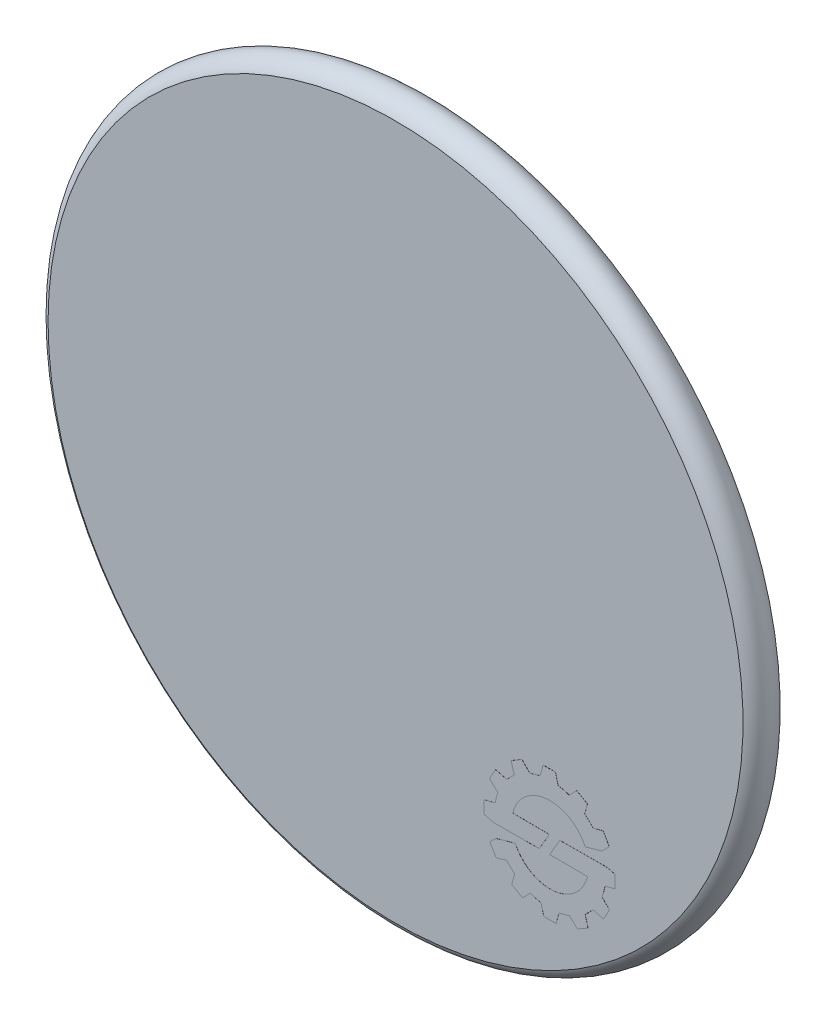
SolidWorks part; units mm, degrees
ref_plane "Front Plane" through (0, 0, 0) normal (0, 0, 1) x (1, 0, 0)
ref_plane "Top Plane" through (0, 0, 0) normal (0, 1, 0) x (1, 0, 0)
ref_plane "Right Plane" through (0, 0, 0) normal (1, 0, 0) x (0, 0, -1)
sketch "Sketch1" plane through (0, 0, 0) normal (0, 1, 0) x (1, 0, 0)
  line L0 (0, 0) -> (-40, 0)
  line L3 (-40, 0) -> (-42, 1.5)
  line L4 (0, 0) -> (0, -3)
  line L5 (0, -3) -> (-42, -3)
  line L6 (-42, -3) -> (-44.5, -3)
  line L8 (-44.5, 1.5) -> (-42, 1.5)
  arc A0 (-44.5, 1.5) -> (-44.5, -3) centre (-43.5625, -0.75) ccw
  dimension "D1" = 40
  dimension "D2" = 42
revolve "Revolve1" add sketch "Sketch1" angle 360 about L4
sketch "Sketch3" plane through (0, 0, 0) normal (0, 0, -1) x (-1, 0, 0)
  line L2 (23.1051, 6.1442) -> (23.4909, 5.3961)
  line L3 (23.4909, 5.3961) -> (22.7778, 4.7181)
  line L4 (-2.9032, -5.6502) -> (-4.1657, -5.0774)
  line L5 (-4.1657, -5.0774) -> (-4.5047, -4.3643)
  line L6 (-4.5047, -4.3643) -> (-4.8436, -3.6513)
  line L7 (-4.8436, -3.6513) -> (-4.2709, -2.5058)
  line L8 (-6.8776, -7.8243) -> (-6.8425, -8.5608)
  line L9 (-6.8425, -8.5608) -> (-7.8244, -9.4024)
  line L10 (-12.0559, -15.5158) -> (-12.4884, -16.334)
  line L11 (-12.4884, -16.334) -> (-12.4767, -17.877)
  line L12 (1.9244, -10.618) -> (3.7596, -10.6531)
  line L13 (3.7596, -10.6531) -> (4.7648, -11.6818)
  line L14 (-6.3749, -9.3322) -> (-5.8606, -8.9114)
  line L15 (-5.8606, -8.9114) -> (-5.5333, -9.1452)
  line L16 (11.416, -24.7386) -> (10.7731, -24.7502)
  line L17 (10.7731, -24.7502) -> (10.7965, -24.2359)
  line L18 (-8.1049, 2.9063) -> (-8.4439, 3.3271)
  line L19 (-8.4439, 3.3271) -> (-8.1049, 3.5726)
  arc A0 (-6.784, 21.8427) -> (7.1261, 21.3752) centre (-0.73, -5.1957) cw
  arc A1 (-9.5661, 22.322) -> (8.6573, 22.8831) centre (0.1955, 1.4952) cw
  spline S84 degree 3 poles (7.1261, 21.3752) (7.617, 21.118) (8.3067, 20.6855) (8.6456, 20.4167) knots 0 0 0 0 1 1 1 1
  spline S85 degree 3 poles (8.6456, 20.4167) (9.6977, 19.5867) (11.1354, 18.1256) (11.4744, 17.5411) knots 0 0 0 0 1 1 1 1
  spline S86 degree 3 poles (11.4744, 17.5411) (12.655, 15.5189) (15.0162, 13.0642) (17.132, 11.6732) knots 0 0 0 0 1 1 1 1
  spline S87 degree 3 poles (17.132, 11.6732) (17.9268, 11.1589) (18.6399, 10.7264) (18.7217, 10.7264) knots 0 0 0 0 1 1 1 1
  spline S88 degree 3 poles (18.7217, 10.7264) (18.8035, 10.7264) (18.9321, 10.6445) (19.0256, 10.5393) knots 0 0 0 0 1 1 1 1
  spline S89 degree 3 poles (19.0256, 10.5393) (19.1074, 10.4458) (19.3763, 10.2588) (19.6218, 10.1302) knots 0 0 0 0 1 1 1 1
  spline S90 degree 3 poles (19.6218, 10.1302) (19.8672, 10.0016) (20.1712, 9.8029) (20.2764, 9.6977) knots 0 0 0 0 1 1 1 1
  spline S91 degree 3 poles (20.2764, 9.6977) (20.3816, 9.5925) (20.7322, 9.2886) (21.0478, 9.0431) knots 0 0 0 0 1 1 1 1
  spline S92 degree 3 poles (21.0478, 9.0431) (21.6323, 8.5522) (22.4389, 7.4183) (23.1051, 6.1442) knots 0 0 0 0 1 1 1 1
  spline S93 degree 3 poles (22.7778, 4.7181) (21.9479, 3.935) (21.6206, 3.3388) (21.5154, 2.4271) knots 0 0 0 0 1 1 1 1
  spline S94 degree 3 poles (21.5154, 2.4271) (21.3985, 1.3867) (21.5855, 0.9192) (22.4739, 0.1009) knots 0 0 0 0 1 1 1 1
  spline S95 degree 3 poles (22.4739, 0.1009) (23.222, -0.5771) (23.2454, -0.6238) (23.1168, -0.9394) knots 0 0 0 0 1 1 1 1
  spline S96 degree 3 poles (23.1168, -0.9394) (22.7895, -1.7226) (20.8258, -3.476) (19.5399, -4.1189) knots 0 0 0 0 1 1 1 1
  spline S97 degree 3 poles (19.5399, -4.1189) (19.1542, -4.3176) (18.7568, -4.528) (18.6633, -4.5864) knots 0 0 0 0 1 1 1 1
  spline S98 degree 3 poles (18.6633, -4.5864) (18.1606, -4.8904) (16.2436, -5.5216) (15.7877, -5.5216) knots 0 0 0 0 1 1 1 1
  spline S99 degree 3 poles (15.7877, -5.5216) (15.6241, -5.5216) (15.3903, -5.58) (15.2734, -5.6385) knots 0 0 0 0 1 1 1 1
  spline S100 degree 3 poles (15.2734, -5.6385) (14.3149, -6.1528) (9.6275, -6.3515) (9.1717, -5.8956) knots 0 0 0 0 1 1 1 1
  spline S101 degree 3 poles (9.1717, -5.8956) (9.0898, -5.8138) (9.0314, -5.3229) (9.0314, -4.6215) knots 0 0 0 0 1 1 1 1
  spline S102 degree 3 poles (9.0314, -4.6215) (9.0197, -3.324) (8.7859, -2.646) (8.3183, -2.5291) knots 0 0 0 0 1 1 1 1
  spline S103 degree 3 poles (8.3183, -2.5291) (7.8742, -2.4239) (7.5936, -2.5759) (7.1377, -3.1954) knots 0 0 0 0 1 1 1 1
  spline S104 degree 3 poles (7.1377, -3.1954) (6.752, -3.7331) (6.7169, -3.8266) (6.7637, -4.3994) knots 0 0 0 0 1 1 1 1
  spline S105 degree 3 poles (6.7637, -4.3994) (6.8104, -4.9371) (6.8806, -5.0891) (7.2429, -5.4398) knots 0 0 0 0 1 1 1 1
  spline S106 degree 3 poles (7.2429, -5.4398) (7.4767, -5.6618) (7.6754, -5.8956) (7.6754, -5.9658) knots 0 0 0 0 1 1 1 1
  spline S107 degree 3 poles (7.6754, -5.9658) (7.6754, -6.0242) (7.465, -6.0827) (7.2196, -6.0827) knots 0 0 0 0 1 1 1 1
  spline S108 degree 3 poles (7.2196, -6.0827) (6.9624, -6.0827) (6.5182, -6.1762) (6.2143, -6.2697) knots 0 0 0 0 1 1 1 1
  spline S109 degree 3 poles (6.2143, -6.2697) (5.9221, -6.3749) (5.6065, -6.4567) (5.5246, -6.4567) knots 0 0 0 0 1 1 1 1
  spline S110 degree 3 poles (5.5246, -6.4567) (5.4311, -6.4567) (5.209, -6.5385) (5.0337, -6.632) knots 0 0 0 0 1 1 1 1
  spline S111 degree 3 poles (5.0337, -6.632) (4.7648, -6.7723) (4.4492, -6.7957) (3.5258, -6.7489) knots 0 0 0 0 1 1 1 1
  spline S112 degree 3 poles (3.5258, -6.7489) (2.8829, -6.7022) (2.0997, -6.6204) (1.7724, -6.5619) knots 0 0 0 0 1 1 1 1
  spline S113 degree 3 poles (1.7724, -6.5619) (1.4568, -6.5035) (0.6736, -6.4333) (0.0307, -6.3983) knots 0 0 0 0 1 1 1 1
  spline S114 degree 3 poles (0.0307, -6.3983) (-0.6005, -6.3749) (-1.1499, -6.3164) (-1.1849, -6.2814) knots 0 0 0 0 1 1 1 1
  spline S115 degree 3 poles (-1.1849, -6.2814) (-1.22, -6.2463) (-1.3369, -6.2229) (-1.4421, -6.2229) knots 0 0 0 0 1 1 1 1
  spline S116 degree 3 poles (-1.4421, -6.2229) (-1.559, -6.2229) (-2.2136, -5.9658) (-2.9032, -5.6502) knots 0 0 0 0 1 1 1 1
  spline S117 degree 3 poles (-4.2709, -2.5058) (-3.6397, -1.2433) (-3.5228, -0.8576) (-3.2539, 0.849) knots 0 0 0 0 1 1 1 1
  spline S118 degree 3 poles (-3.2539, 0.849) (-3.102, 1.7958) (-3.0903, 2.2751) (-3.1838, 3.4206) knots 0 0 0 0 1 1 1 1
  spline S119 degree 3 poles (-3.1838, 3.4206) (-3.4293, 6.2611) (-3.5578, 6.8105) (-4.0371, 7.1495) knots 0 0 0 0 1 1 1 1
  spline S120 degree 3 poles (-4.0371, 7.1495) (-4.5514, 7.5118) (-5.6034, 7.2897) (-5.8957, 6.7404) knots 0 0 0 0 1 1 1 1
  spline S121 degree 3 poles (-5.8957, 6.7404) (-5.9892, 6.5533) (-5.9892, 5.9689) (-5.884, 4.4843) knots 0 0 0 0 1 1 1 1
  spline S122 degree 3 poles (-5.884, 4.4843) (-5.7788, 2.8245) (-5.7788, 2.3219) (-5.919, 1.5504) knots 0 0 0 0 1 1 1 1
  spline S123 degree 3 poles (-5.919, 1.5504) (-6.0126, 1.036) (-6.1411, 0.4983) (-6.2113, 0.3581) knots 0 0 0 0 1 1 1 1
  spline S124 degree 3 poles (-6.2113, 0.3581) (-6.2931, 0.2178) (-6.3515, -0.0744) (-6.3515, -0.2848) knots 0 0 0 0 1 1 1 1
  spline S125 degree 3 poles (-6.3515, -0.2848) (-6.3515, -0.7407) (-6.6321, -1.7226) (-6.8776, -2.085) knots 0 0 0 0 1 1 1 1
  spline S126 degree 3 poles (-6.8776, -2.085) (-6.9711, -2.2252) (-7.123, -2.7162) (-7.2165, -3.1604) knots 0 0 0 0 1 1 1 1
  spline S127 degree 3 poles (-7.2165, -3.1604) (-7.5088, -4.5397) (-8.14, -5.5566) (-9.0284, -6.0827) knots 0 0 0 0 1 1 1 1
  spline S128 degree 3 poles (-9.0284, -6.0827) (-9.3206, -6.2463) (-9.8583, -6.6087) (-10.209, -6.8775) knots 0 0 0 0 1 1 1 1
  spline S129 degree 3 poles (-10.209, -6.8775) (-10.9688, -7.4503) (-11.635, -7.801) (-12.1961, -7.9179) knots 0 0 0 0 1 1 1 1
  spline S130 degree 3 poles (-12.1961, -7.9179) (-12.4182, -7.9646) (-12.6871, -8.0698) (-12.7806, -8.1516) knots 0 0 0 0 1 1 1 1
  spline S131 degree 3 poles (-12.7806, -8.1516) (-12.8741, -8.2335) (-13.2832, -8.362) (-13.6806, -8.4439) knots 0 0 0 0 1 1 1 1
  spline S132 degree 3 poles (-13.6806, -8.4439) (-14.0781, -8.514) (-14.5924, -8.6426) (-14.8028, -8.7361) knots 0 0 0 0 1 1 1 1
  spline S133 degree 3 poles (-14.8028, -8.7361) (-15.0249, -8.8296) (-15.5509, -8.9348) (-15.9717, -8.9816) knots 0 0 0 0 1 1 1 1
  spline S134 degree 3 poles (-15.9717, -8.9816) (-16.6614, -9.0517) (-16.8017, -9.0283) (-17.3277, -8.7478) knots 0 0 0 0 1 1 1 1
  spline S135 degree 3 poles (-17.3277, -8.7478) (-17.655, -8.5841) (-17.9823, -8.4439) (-18.0524, -8.4439) knots 0 0 0 0 1 1 1 1
  spline S136 degree 3 poles (-18.0524, -8.4439) (-18.1225, -8.4439) (-18.4264, -8.2685) (-18.7304, -8.0581) knots 0 0 0 0 1 1 1 1
  spline S137 degree 3 poles (-18.7304, -8.0581) (-19.0226, -7.8477) (-19.4083, -7.6022) (-19.572, -7.5204) knots 0 0 0 0 1 1 1 1
  spline S138 degree 3 poles (-19.572, -7.5204) (-19.7473, -7.4386) (-20.0279, -7.2282) (-20.2149, -7.0645) knots 0 0 0 0 1 1 1 1
  spline S139 degree 3 poles (-20.2149, -7.0645) (-20.5656, -6.7256) (-21.5007, -6.106) (-21.641, -6.106) knots 0 0 0 0 1 1 1 1
  spline S140 degree 3 poles (-21.641, -6.106) (-21.6877, -6.106) (-21.7929, -6.0008) (-21.8748, -5.8722) knots 0 0 0 0 1 1 1 1
  spline S141 degree 3 poles (-21.8748, -5.8722) (-21.9566, -5.7437) (-22.0852, -5.6385) (-22.167, -5.6385) knots 0 0 0 0 1 1 1 1
  spline S142 degree 3 poles (-22.167, -5.6385) (-22.2371, -5.6385) (-22.6462, -5.3579) (-23.067, -5.0189) knots 0 0 0 0 1 1 1 1
  spline S143 degree 3 poles (-23.067, -5.0189) (-23.6866, -4.528) (-23.9087, -4.2358) (-24.271, -3.5227) knots 0 0 0 0 1 1 1 1
  spline S144 degree 3 poles (-24.271, -3.5227) (-24.7269, -2.6344) (-24.7269, -2.6227) (-24.7269, -1.1849) knots 0 0 0 0 1 1 1 1
  spline S145 degree 3 poles (-24.7269, -1.1849) (-24.7269, 0.3698) (-24.4697, 1.7491) (-23.9788, 2.7076) knots 0 0 0 0 1 1 1 1
  spline S146 degree 3 poles (-23.9788, 2.7076) (-23.6164, 3.4323) (-22.8099, 4.6363) (-22.2956, 5.2441) knots 0 0 0 0 1 1 1 1
  spline S147 degree 3 poles (-22.2956, 5.2441) (-22.0501, 5.5481) (-21.7111, 5.9572) (-21.5475, 6.1676) knots 0 0 0 0 1 1 1 1
  spline S148 degree 3 poles (-21.5475, 6.1676) (-21.3838, 6.3663) (-21.1617, 6.6468) (-21.0331, 6.7871) knots 0 0 0 0 1 1 1 1
  spline S149 degree 3 poles (-21.0331, 6.7871) (-20.7877, 7.0677) (-19.6304, 8.5756) (-19.2681, 9.0782) knots 0 0 0 0 1 1 1 1
  spline S150 degree 3 poles (-19.2681, 9.0782) (-19.1395, 9.2535) (-18.7537, 9.6276) (-18.4148, 9.9198) knots 0 0 0 0 1 1 1 1
  spline S151 degree 3 poles (-18.4148, 9.9198) (-17.2926, 10.8432) (-16.7666, 11.4628) (-16.0769, 12.6551) knots 0 0 0 0 1 1 1 1
  spline S152 degree 3 poles (-16.0769, 12.6551) (-15.1184, 14.2916) (-15.1418, 14.2565) (-15.0717, 14.5955) knots 0 0 0 0 1 1 1 1
  spline S153 degree 3 poles (-15.0717, 14.5955) (-15.0366, 14.7708) (-14.8145, 15.1332) (-14.5924, 15.402) knots 0 0 0 0 1 1 1 1
  spline S154 degree 3 poles (-14.5924, 15.402) (-14.3703, 15.6709) (-14.2184, 15.9397) (-14.2534, 15.9982) knots 0 0 0 0 1 1 1 1
  spline S155 degree 3 poles (-14.2534, 15.9982) (-14.4755, 16.3722) (-12.6286, 18.1373) (-10.4428, 19.6452) knots 0 0 0 0 1 1 1 1
  spline S156 degree 3 poles (-10.4428, 19.6452) (-9.3089, 20.4167) (-7.7776, 21.3635) (-7.6607, 21.3635) knots 0 0 0 0 1 1 1 1
  spline S157 degree 3 poles (-7.6607, 21.3635) (-7.6023, 21.3635) (-7.4854, 21.4453) (-7.4036, 21.5388) knots 0 0 0 0 1 1 1 1
  spline S158 degree 3 poles (-7.4036, 21.5388) (-7.3217, 21.6323) (-7.0412, 21.7726) (-6.784, 21.8427) knots 0 0 0 0 1 1 1 1
  spline S163 degree 3 poles (-9.5661, 22.322) (-11.074, 21.3167) (-14.0664, 18.9789) (-14.4054, 18.5464) knots 0 0 0 0 1 1 1 1
  spline S164 degree 3 poles (-14.4054, 18.5464) (-14.6275, 18.2659) (-14.8846, 17.9853) (-14.9665, 17.9386) knots 0 0 0 0 1 1 1 1
  spline S165 degree 3 poles (-14.9665, 17.9386) (-15.0483, 17.8918) (-15.2002, 17.6814) (-15.3054, 17.471) knots 0 0 0 0 1 1 1 1
  spline S166 degree 3 poles (-15.3054, 17.471) (-15.4106, 17.2606) (-15.8198, 16.6995) (-16.2172, 16.2203) knots 0 0 0 0 1 1 1 1
  spline S167 degree 3 poles (-16.2172, 16.2203) (-16.6029, 15.741) (-17.4796, 14.6188) (-18.1576, 13.7188) knots 0 0 0 0 1 1 1 1
  spline S168 degree 3 poles (-18.1576, 13.7188) (-18.8356, 12.8187) (-19.759, 11.755) (-20.25, 11.3225) knots 0 0 0 0 1 1 1 1
  spline S169 degree 3 poles (-20.25, 11.3225) (-22.845, 8.9964) (-24.9373, 6.8572) (-24.9373, 6.5416) knots 0 0 0 0 1 1 1 1
  spline S170 degree 3 poles (-24.9373, 6.5416) (-24.9373, 6.4715) (-24.9724, 6.4014) (-25.0191, 6.378) knots 0 0 0 0 1 1 1 1
  spline S171 degree 3 poles (-25.0191, 6.378) (-25.1828, 6.3079) (-26.1062, 4.8818) (-26.1764, 4.5779) knots 0 0 0 0 1 1 1 1
  spline S172 degree 3 poles (-26.1764, 4.5779) (-26.2231, 4.4259) (-26.4335, 3.935) (-26.6439, 3.5025) knots 0 0 0 0 1 1 1 1
  spline S173 degree 3 poles (-26.6439, 3.5025) (-26.866, 3.07) (-27.0414, 2.579) (-27.0414, 2.4154) knots 0 0 0 0 1 1 1 1
  spline S174 degree 3 poles (-27.0414, 2.4154) (-27.0414, 2.24) (-27.1232, 2.0413) (-27.2284, 1.9478) knots 0 0 0 0 1 1 1 1
  spline S175 degree 3 poles (-27.2284, 1.9478) (-27.3336, 1.866) (-27.3803, 1.7023) (-27.3453, 1.5737) knots 0 0 0 0 1 1 1 1
  spline S176 degree 3 poles (-27.3453, 1.5737) (-27.3102, 1.4452) (-27.3453, 1.2348) (-27.4037, 1.1062) knots 0 0 0 0 1 1 1 1
  spline S177 degree 3 poles (-27.4037, 1.1062) (-27.6024, 0.7555) (-27.6258, -2.12) (-27.4505, -2.5642) knots 0 0 0 0 1 1 1 1
  spline S178 degree 3 poles (-27.4505, -2.5642) (-27.3687, -2.7629) (-27.3219, -2.9616) (-27.357, -2.985) knots 0 0 0 0 1 1 1 1
  spline S179 degree 3 poles (-27.357, -2.985) (-27.4505, -3.0902) (-27.1349, -4.0487) (-26.7141, -4.9371) knots 0 0 0 0 1 1 1 1
  spline S180 degree 3 poles (-26.7141, -4.9371) (-25.627, -7.2048) (-24.2476, -8.5724) (-22.202, -9.4374) knots 0 0 0 0 1 1 1 1
  spline S181 degree 3 poles (-22.202, -9.4374) (-21.7462, -9.6245) (-21.1266, -9.9985) (-20.811, -10.2674) knots 0 0 0 0 1 1 1 1
  spline S182 degree 3 poles (-20.811, -10.2674) (-19.5837, -11.3194) (-18.0524, -11.8688) (-16.4627, -11.822) knots 0 0 0 0 1 1 1 1
  spline S183 degree 3 poles (-16.4627, -11.822) (-15.9951, -11.8103) (-15.4106, -11.7285) (-15.1652, -11.635) knots 0 0 0 0 1 1 1 1
  spline S184 degree 3 poles (-15.1652, -11.635) (-14.908, -11.5415) (-14.4755, -11.3895) (-14.1833, -11.296) knots 0 0 0 0 1 1 1 1
  spline S185 degree 3 poles (-14.1833, -11.296) (-13.8911, -11.2025) (-13.4469, -11.0038) (-13.1897, -10.8401) knots 0 0 0 0 1 1 1 1
  spline S186 degree 3 poles (-13.1897, -10.8401) (-12.9325, -10.6882) (-12.278, -10.3141) (-11.7286, -10.0102) knots 0 0 0 0 1 1 1 1
  spline S187 degree 3 poles (-11.7286, -10.0102) (-10.6298, -9.4024) (-10.2674, -9.1452) (-9.1803, -8.2451) knots 0 0 0 0 1 1 1 1
  spline S188 degree 3 poles (-9.1803, -8.2451) (-8.7829, -7.9062) (-8.3855, -7.6256) (-8.3036, -7.6256) knots 0 0 0 0 1 1 1 1
  spline S189 degree 3 poles (-8.3036, -7.6256) (-8.2335, -7.6139) (-7.9646, -7.3685) (-7.7309, -7.0645) knots 0 0 0 0 1 1 1 1
  spline S190 degree 3 poles (-7.7309, -7.0645) (-7.4854, -6.7606) (-7.1698, -6.3866) (-7.0178, -6.2229) knots 0 0 0 0 1 1 1 1
  spline S191 degree 3 poles (-7.0178, -6.2229) (-6.8776, -6.0593) (-6.6087, -5.732) (-6.4217, -5.4865) knots 0 0 0 0 1 1 1 1
  spline S192 degree 3 poles (-6.4217, -5.4865) (-6.2347, -5.2527) (-6.0126, -5.054) (-5.9307, -5.054) knots 0 0 0 0 1 1 1 1
  spline S193 degree 3 poles (-5.9307, -5.054) (-5.6502, -5.054) (-5.7554, -5.4514) (-6.1061, -5.7904) knots 0 0 0 0 1 1 1 1
  spline S194 degree 3 poles (-6.1061, -5.7904) (-6.6555, -6.3047) (-6.9126, -6.9827) (-6.8776, -7.8243) knots 0 0 0 0 1 1 1 1
  spline S195 degree 3 poles (-7.8244, -9.4024) (-8.3971, -9.8933) (-9.005, -10.5596) (-9.2738, -10.957) knots 0 0 0 0 1 1 1 1
  spline S196 degree 3 poles (-9.2738, -10.957) (-9.8349, -11.8337) (-10.5246, -12.8156) (-10.9337, -13.365) knots 0 0 0 0 1 1 1 1
  spline S197 degree 3 poles (-10.9337, -13.365) (-11.109, -13.5871) (-11.3428, -13.9845) (-11.448, -14.2417) knots 0 0 0 0 1 1 1 1
  spline S198 degree 3 poles (-11.448, -14.2417) (-11.5532, -14.4872) (-11.8221, -15.0599) (-12.0559, -15.5158) knots 0 0 0 0 1 1 1 1
  spline S199 degree 3 poles (-12.4767, -17.877) (-12.4767, -19.0226) (-12.5117, -19.4317) (-12.6169, -19.4317) knots 0 0 0 0 1 1 1 1
  spline S200 degree 3 poles (-12.6169, -19.4317) (-12.839, -19.4317) (-13.4702, -18.6485) (-13.7391, -18.0407) knots 0 0 0 0 1 1 1 1
  spline S201 degree 3 poles (-13.7391, -18.0407) (-14.9898, -15.1768) (-15.5275, -14.6157) (-16.6263, -15.0599) knots 0 0 0 0 1 1 1 1
  spline S202 degree 3 poles (-16.6263, -15.0599) (-17.4446, -15.3872) (-17.9238, -16.4393) (-17.9238, -17.877) knots 0 0 0 0 1 1 1 1
  spline S203 degree 3 poles (-17.9238, -17.877) (-17.9238, -18.1576) (-17.9823, -18.6251) (-18.0524, -18.9057) knots 0 0 0 0 1 1 1 1
  spline S204 degree 3 poles (-18.0524, -18.9057) (-18.1576, -19.3265) (-18.1459, -19.5252) (-17.9939, -19.9694) knots 0 0 0 0 1 1 1 1
  spline S205 degree 3 poles (-17.9939, -19.9694) (-17.8186, -20.4954) (-17.0237, -21.7695) (-16.8835, -21.7695) knots 0 0 0 0 1 1 1 1
  spline S206 degree 3 poles (-16.8835, -21.7695) (-16.8367, -21.7695) (-16.5445, -21.9916) (-16.2289, -22.2605) knots 0 0 0 0 1 1 1 1
  spline S207 degree 3 poles (-16.2289, -22.2605) (-15.5743, -22.7982) (-13.3417, -23.9203) (-12.5468, -24.0957) knots 0 0 0 0 1 1 1 1
  spline S208 degree 3 poles (-12.5468, -24.0957) (-12.2546, -24.1658) (-11.8221, -24.2242) (-11.5766, -24.2242) knots 0 0 0 0 1 1 1 1
  spline S209 degree 3 poles (-11.5766, -24.2242) (-11.2961, -24.2242) (-11.109, -24.2827) (-11.074, -24.3996) knots 0 0 0 0 1 1 1 1
  spline S210 degree 3 poles (-11.074, -24.3996) (-11.0155, -24.5515) (-10.6882, -24.8087) (-9.4609, -25.7204) knots 0 0 0 0 1 1 1 1
  spline S211 degree 3 poles (-9.4609, -25.7204) (-9.2621, -25.8607) (-8.8881, -26.0361) (-8.6309, -26.1062) knots 0 0 0 0 1 1 1 1
  spline S212 degree 3 poles (-8.6309, -26.1062) (-8.1984, -26.2231) (-6.936, -26.7491) (-5.8255, -27.2751) knots 0 0 0 0 1 1 1 1
  spline S213 degree 3 poles (-5.8255, -27.2751) (-5.1826, -27.579) (-4.4462, -27.7193) (-3.5812, -27.731) knots 0 0 0 0 1 1 1 1
  spline S214 degree 3 poles (-3.5812, -27.731) (-3.1838, -27.731) (-2.7279, -27.7894) (-2.5643, -27.8596) knots 0 0 0 0 1 1 1 1
  spline S215 degree 3 poles (-2.5643, -27.8596) (-2.3422, -27.9648) (-2.1434, -27.9648) (-1.7577, -27.8596) knots 0 0 0 0 1 1 1 1
  spline S216 degree 3 poles (-1.7577, -27.8596) (-1.0797, -27.6608) (-0.4135, -27.8479) (0.3697, -28.4206) knots 0 0 0 0 1 1 1 1
  spline S217 degree 3 poles (0.3697, -28.4206) (1.7841, -29.461) (2.053, -29.6012) (3.1401, -29.8818) knots 0 0 0 0 1 1 1 1
  spline S218 degree 3 poles (3.1401, -29.8818) (4.2038, -30.1623) (5.7234, -30.0922) (6.6702, -29.7298) knots 0 0 0 0 1 1 1 1
  spline S219 degree 3 poles (6.6702, -29.7298) (7.6287, -29.3558) (9.2535, -27.8829) (9.686, -27.0179) knots 0 0 0 0 1 1 1 1
  spline S220 degree 3 poles (9.686, -27.0179) (10.2237, -25.9192) (10.212, -25.9308) (10.9484, -26.3049) knots 0 0 0 0 1 1 1 1
  spline S221 degree 3 poles (10.9484, -26.3049) (11.5329, -26.5971) (11.7082, -26.6205) (12.8771, -26.6205) knots 0 0 0 0 1 1 1 1
  spline S222 degree 3 poles (12.8771, -26.6205) (14.1512, -26.6088) (14.1746, -26.6088) (14.9695, -26.1646) knots 0 0 0 0 1 1 1 1
  spline S223 degree 3 poles (14.9695, -26.1646) (16.2436, -25.4516) (17.1437, -24.3177) (17.4827, -22.9969) knots 0 0 0 0 1 1 1 1
  spline S224 degree 3 poles (17.4827, -22.9969) (17.8216, -21.6643) (17.7515, -19.5018) (17.3073, -17.9355) knots 0 0 0 0 1 1 1 1
  spline S225 degree 3 poles (17.3073, -17.9355) (17.0618, -17.0822) (16.4189, -16.112) (15.7643, -15.6444) knots 0 0 0 0 1 1 1 1
  spline S226 degree 3 poles (15.7643, -15.6444) (15.2968, -15.2937) (15.0747, -15.2236) (14.0694, -15.095) knots 0 0 0 0 1 1 1 1
  spline S227 degree 3 poles (14.0694, -15.095) (12.4212, -14.8846) (11.7199, -15.0482) (10.8198, -15.8197) knots 0 0 0 0 1 1 1 1
  spline S228 degree 3 poles (10.8198, -15.8197) (10.4575, -16.1353) (10.1302, -16.3925) (10.0834, -16.3925) knots 0 0 0 0 1 1 1 1
  spline S229 degree 3 poles (10.0834, -16.3925) (10.0483, -16.3925) (10.0133, -16.2873) (10.0133, -16.1704) knots 0 0 0 0 1 1 1 1
  spline S230 degree 3 poles (10.0133, -16.1704) (10.0133, -16.0418) (9.8029, -15.5275) (9.5457, -15.0249) knots 0 0 0 0 1 1 1 1
  spline S231 degree 3 poles (9.5457, -15.0249) (9.1717, -14.2884) (8.821, -13.8443) (7.6871, -12.7104) knots 0 0 0 0 1 1 1 1
  spline S232 degree 3 poles (7.6871, -12.7104) (6.2961, -11.3077) (5.3025, -10.431) (5.0921, -10.431) knots 0 0 0 0 1 1 1 1
  spline S233 degree 3 poles (5.0921, -10.431) (4.8817, -10.431) (4.9869, -10.1037) (5.2675, -9.9284) knots 0 0 0 0 1 1 1 1
  spline S234 degree 3 poles (5.2675, -9.9284) (5.4194, -9.8232) (5.6532, -9.4959) (5.7935, -9.2037) knots 0 0 0 0 1 1 1 1
  spline S235 degree 3 poles (5.7935, -9.2037) (6.0623, -8.6192) (6.0507, -8.1516) (5.735, -7.6607) knots 0 0 0 0 1 1 1 1
  spline S236 degree 3 poles (5.735, -7.6607) (5.5831, -7.4152) (5.5948, -7.4035) (6.3429, -7.3334) knots 0 0 0 0 1 1 1 1
  spline S237 degree 3 poles (6.3429, -7.3334) (7.2429, -7.2282) (7.8859, -7.3217) (8.4703, -7.6139) knots 0 0 0 0 1 1 1 1
  spline S238 degree 3 poles (8.4703, -7.6139) (9.0898, -7.9179) (10.3289, -8.0231) (12.8771, -7.988) knots 0 0 0 0 1 1 1 1
  spline S239 degree 3 poles (12.8771, -7.988) (14.6539, -7.9529) (15.2383, -7.9062) (15.7994, -7.7308) knots 0 0 0 0 1 1 1 1
  spline S240 degree 3 poles (15.7994, -7.7308) (16.1852, -7.6139) (16.6293, -7.5087) (16.793, -7.5087) knots 0 0 0 0 1 1 1 1
  spline S241 degree 3 poles (16.793, -7.5087) (16.9566, -7.5087) (17.1904, -7.4386) (17.319, -7.3568) knots 0 0 0 0 1 1 1 1
  spline S242 degree 3 poles (17.319, -7.3568) (17.4476, -7.2633) (17.8918, -7.0762) (18.3126, -6.9243) knots 0 0 0 0 1 1 1 1
  spline S243 degree 3 poles (18.3126, -6.9243) (19.5166, -6.4801) (20.0075, -6.1645) (21.1063, -5.1475) knots 0 0 0 0 1 1 1 1
  spline S244 degree 3 poles (21.1063, -5.1475) (21.457, -4.8202) (21.9245, -4.4812) (22.1466, -4.3877) knots 0 0 0 0 1 1 1 1
  spline S245 degree 3 poles (22.1466, -4.3877) (23.0934, -3.9903) (24.3091, -2.7746) (24.9286, -1.6174) knots 0 0 0 0 1 1 1 1
  spline S246 degree 3 poles (24.9286, -1.6174) (25.1391, -1.22) (25.2793, -1.1148) (25.6884, -0.9979) knots 0 0 0 0 1 1 1 1
  spline S247 degree 3 poles (25.6884, -0.9979) (25.969, -0.9277) (26.5651, -0.6823) (27.0093, -0.4602) knots 0 0 0 0 1 1 1 1
  spline S248 degree 3 poles (27.0093, -0.4602) (27.7808, -0.0744) (27.8392, -0.016) (28.0613, 0.5802) knots 0 0 0 0 1 1 1 1
  spline S249 degree 3 poles (28.0613, 0.5802) (28.225, 1.0244) (28.2834, 1.4452) (28.2717, 2.0647) knots 0 0 0 0 1 1 1 1
  spline S250 degree 3 poles (28.2717, 2.0647) (28.2484, 2.8011) (28.1899, 3.0115) (27.8977, 3.4674) knots 0 0 0 0 1 1 1 1
  spline S251 degree 3 poles (27.8977, 3.4674) (27.3951, 4.2623) (27.1028, 4.5194) (26.308, 4.8935) knots 0 0 0 0 1 1 1 1
  spline S252 degree 3 poles (26.308, 4.8935) (25.9105, 5.0688) (25.5482, 5.3143) (25.5014, 5.4312) knots 0 0 0 0 1 1 1 1
  spline S253 degree 3 poles (25.5014, 5.4312) (25.4547, 5.5481) (25.3962, 5.9338) (25.3728, 6.2962) knots 0 0 0 0 1 1 1 1
  spline S254 degree 3 poles (25.3728, 6.2962) (25.3378, 7.0326) (25.0455, 7.7106) (24.578, 8.1431) knots 0 0 0 0 1 1 1 1
  spline S255 degree 3 poles (24.578, 8.1431) (24.4143, 8.3067) (24.2741, 8.482) (24.2741, 8.5405) knots 0 0 0 0 1 1 1 1
  spline S256 degree 3 poles (24.2741, 8.5405) (24.2741, 8.7158) (23.5493, 9.499) (22.8012, 10.1185) knots 0 0 0 0 1 1 1 1
  spline S257 degree 3 poles (22.8012, 10.1185) (21.9245, 10.8549) (20.5569, 11.6966) (19.0607, 12.433) knots 0 0 0 0 1 1 1 1
  spline S258 degree 3 poles (19.0607, 12.433) (17.4593, 13.2045) (16.6878, 13.672) (16.1852, 14.1747) knots 0 0 0 0 1 1 1 1
  spline S259 degree 3 poles (16.1852, 14.1747) (15.741, 14.6072) (13.5551, 17.7632) (12.8771, 18.9438) knots 0 0 0 0 1 1 1 1
  spline S260 degree 3 poles (12.8771, 18.9438) (12.0121, 20.4517) (11.5212, 21.0011) (10.7497, 21.3167) knots 0 0 0 0 1 1 1 1
  spline S261 degree 3 poles (10.7497, 21.3167) (10.5393, 21.4102) (10.1419, 21.7025) (9.8613, 21.9713) knots 0 0 0 0 1 1 1 1
  spline S262 degree 3 poles (9.8613, 21.9713) (9.5691, 22.2519) (9.0314, 22.661) (8.6573, 22.8831) knots 0 0 0 0 1 1 1 1
  spline S265 degree 3 poles (24.7416, 3.8882) (25.2443, 3.2921) (23.748, 2.2751) (23.187, 2.8362) knots 0 0 0 0 1 1 1 1
  spline S266 degree 3 poles (23.187, 2.8362) (22.8947, 3.1284) (22.9415, 3.4206) (23.3506, 3.7596) knots 0 0 0 0 1 1 1 1
  spline S267 degree 3 poles (23.3506, 3.7596) (23.7597, 4.1103) (24.5078, 4.1804) (24.7416, 3.8882) knots 0 0 0 0 1 1 1 1
  spline S287 degree 3 poles (-4.5163, -9.5076) (-4.1423, -9.5777) (-3.4176, -9.7063) (-2.9032, -9.8115) knots 0 0 0 0 1 1 1 1
  spline S288 degree 3 poles (-2.9032, -9.8115) (-2.3889, -9.9167) (-1.7343, -10.0336) (-1.4421, -10.092) knots 0 0 0 0 1 1 1 1
  spline S289 degree 3 poles (-1.4421, -10.092) (-0.5654, -10.244) (-0.2264, -10.3375) (-0.0628, -10.4661) knots 0 0 0 0 1 1 1 1
  spline S290 degree 3 poles (-0.0628, -10.4661) (0.0307, -10.5362) (0.884, -10.6064) (1.9244, -10.618) knots 0 0 0 0 1 1 1 1
  spline S291 degree 3 poles (4.7648, -11.6818) (5.3142, -12.2428) (6.0857, -13.0026) (6.4715, -13.365) knots 0 0 0 0 1 1 1 1
  spline S292 degree 3 poles (6.4715, -13.365) (7.465, -14.2884) (8.2482, -15.5275) (8.3768, -16.3691) knots 0 0 0 0 1 1 1 1
  spline S293 degree 3 poles (8.3768, -16.3691) (8.4352, -16.7315) (8.4703, -17.1406) (8.4352, -17.2692) knots 0 0 0 0 1 1 1 1
  spline S294 degree 3 poles (8.4352, -17.2692) (8.4119, -17.3978) (8.3885, -17.538) (8.3885, -17.5965) knots 0 0 0 0 1 1 1 1
  spline S295 degree 3 poles (8.3885, -17.5965) (8.3768, -17.69) (7.2429, -17.1172) (7.1377, -16.9653) knots 0 0 0 0 1 1 1 1
  spline S296 degree 3 poles (7.1377, -16.9653) (7.0559, -16.8133) (5.8402, -16.8367) (5.2792, -16.9886) knots 0 0 0 0 1 1 1 1
  spline S297 degree 3 poles (5.2792, -16.9886) (4.7298, -17.1406) (4.344, -17.4095) (3.5375, -18.216) knots 0 0 0 0 1 1 1 1
  spline S298 degree 3 poles (3.5375, -18.216) (2.2283, -19.5135) (1.9478, -19.946) (1.4802, -21.4071) knots 0 0 0 0 1 1 1 1
  spline S299 degree 3 poles (1.4802, -21.4071) (1.2581, -22.1319) (1.2581, -22.5877) (1.5153, -22.9034) knots 0 0 0 0 1 1 1 1
  spline S300 degree 3 poles (1.5153, -22.9034) (1.6906, -23.1371) (1.8075, -23.0787) (2.0179, -22.6696) knots 0 0 0 0 1 1 1 1
  spline S301 degree 3 poles (2.0179, -22.6696) (2.1231, -22.4709) (2.4153, -22.0734) (2.6608, -21.8046) knots 0 0 0 0 1 1 1 1
  spline S302 degree 3 poles (2.6608, -21.8046) (2.918, -21.524) (3.1167, -21.2552) (3.1167, -21.1967) knots 0 0 0 0 1 1 1 1
  spline S303 degree 3 poles (3.1167, -21.1967) (3.1167, -21.0448) (4.5661, -20.2499) (4.835, -20.2499) knots 0 0 0 0 1 1 1 1
  spline S304 degree 3 poles (4.835, -20.2499) (4.9636, -20.2499) (5.2324, -20.472) (5.4545, -20.7759) knots 0 0 0 0 1 1 1 1
  spline S305 degree 3 poles (5.4545, -20.7759) (5.6766, -21.0682) (5.887, -21.3019) (5.9455, -21.3019) knots 0 0 0 0 1 1 1 1
  spline S306 degree 3 poles (5.9455, -21.3019) (6.1091, -21.3019) (6.0507, -20.4837) (5.8519, -20.1213) knots 0 0 0 0 1 1 1 1
  spline S307 degree 3 poles (5.8519, -20.1213) (5.7117, -19.8408) (5.7, -19.7239) (5.8169, -19.5953) knots 0 0 0 0 1 1 1 1
  spline S308 degree 3 poles (5.8169, -19.5953) (6.0273, -19.3382) (6.1909, -19.3966) (6.5416, -19.8408) knots 0 0 0 0 1 1 1 1
  spline S309 degree 3 poles (6.5416, -19.8408) (6.9741, -20.3902) (7.1377, -20.3668) (7.0442, -19.7824) knots 0 0 0 0 1 1 1 1
  spline S310 degree 3 poles (7.0442, -19.7824) (6.9741, -19.3499) (6.9858, -19.3148) (7.1728, -19.42) knots 0 0 0 0 1 1 1 1
  spline S311 degree 3 poles (7.1728, -19.42) (7.7456, -19.7239) (8.5404, -20.7409) (8.8794, -21.6292) knots 0 0 0 0 1 1 1 1
  spline S312 degree 3 poles (8.8794, -21.6292) (9.008, -21.9565) (9.0781, -22.4709) (9.0781, -23.1605) knots 0 0 0 0 1 1 1 1
  spline S313 degree 3 poles (9.0781, -23.1605) (9.0781, -24.119) (9.0431, -24.2593) (8.6456, -25.0542) knots 0 0 0 0 1 1 1 1
  spline S314 degree 3 poles (8.6456, -25.0542) (8.0378, -26.2698) (6.939, -27.3569) (5.9455, -27.7193) knots 0 0 0 0 1 1 1 1
  spline S315 degree 3 poles (5.9455, -27.7193) (5.3025, -27.9414) (5.0805, -27.9765) (4.309, -27.8946) knots 0 0 0 0 1 1 1 1
  spline S316 degree 3 poles (4.309, -27.8946) (3.1868, -27.7894) (3.0933, -27.766) (0.3697, -26.679) knots 0 0 0 0 1 1 1 1
  spline S317 degree 3 poles (0.3697, -26.679) (-0.8343, -26.1997) (-1.6876, -25.9308) (-1.9214, -25.9659) knots 0 0 0 0 1 1 1 1
  spline S318 degree 3 poles (-1.9214, -25.9659) (-2.0266, -25.9776) (-2.3539, -25.9075) (-2.6578, -25.8023) knots 0 0 0 0 1 1 1 1
  spline S319 degree 3 poles (-2.6578, -25.8023) (-2.9617, -25.6971) (-3.3007, -25.6386) (-3.4176, -25.6854) knots 0 0 0 0 1 1 1 1
  spline S320 degree 3 poles (-3.4176, -25.6854) (-3.6163, -25.7438) (-5.1242, -25.3931) (-6.41, -24.9957) knots 0 0 0 0 1 1 1 1
  spline S321 degree 3 poles (-6.41, -24.9957) (-6.7256, -24.8905) (-7.4386, -24.5165) (-7.988, -24.1658) knots 0 0 0 0 1 1 1 1
  spline S322 degree 3 poles (-7.988, -24.1658) (-8.5257, -23.8151) (-9.0284, -23.5229) (-9.0985, -23.5229) knots 0 0 0 0 1 1 1 1
  spline S323 degree 3 poles (-9.0985, -23.5229) (-9.2972, -23.5229) (-10.1388, -22.5877) (-10.3492, -22.1202) knots 0 0 0 0 1 1 1 1
  spline S324 degree 3 poles (-10.3492, -22.1202) (-10.8051, -21.1266) (-10.9805, -18.2744) (-10.6415, -17.5965) knots 0 0 0 0 1 1 1 1
  spline S325 degree 3 poles (-10.6415, -17.5965) (-10.5246, -17.3861) (-10.4428, -17.0938) (-10.4428, -16.9419) knots 0 0 0 0 1 1 1 1
  spline S326 degree 3 poles (-10.4428, -16.9419) (-10.4428, -16.7315) (-10.3609, -16.6263) (-10.1388, -16.5795) knots 0 0 0 0 1 1 1 1
  spline S327 degree 3 poles (-10.1388, -16.5795) (-9.5193, -16.4159) (-7.9763, -14.6742) (-7.4854, -13.5871) knots 0 0 0 0 1 1 1 1
  spline S328 degree 3 poles (-7.4854, -13.5871) (-7.0763, -12.687) (-6.9009, -11.2376) (-7.1698, -11.0739) knots 0 0 0 0 1 1 1 1
  spline S329 degree 3 poles (-7.1698, -11.0739) (-7.3568, -10.957) (-7.2984, -10.244) (-7.0763, -9.9868) knots 0 0 0 0 1 1 1 1
  spline S330 degree 3 poles (-7.0763, -9.9868) (-6.9711, -9.8466) (-6.6438, -9.5543) (-6.3749, -9.3322) knots 0 0 0 0 1 1 1 1
  spline S331 degree 3 poles (-5.5333, -9.1452) (-5.3463, -9.2738) (-4.8904, -9.4374) (-4.5163, -9.5076) knots 0 0 0 0 1 1 1 1
  spline S341 degree 3 poles (13.7889, -16.6146) (13.9759, -16.7782) (14.198, -17.0588) (14.2915, -17.2341) knots 0 0 0 0 1 1 1 1
  spline S342 degree 3 poles (14.2915, -17.2341) (14.4785, -17.5848) (14.8058, -17.6783) (14.8058, -17.3861) knots 0 0 0 0 1 1 1 1
  spline S343 degree 3 poles (14.8058, -17.3861) (14.8058, -17.2809) (14.724, -17.0705) (14.6188, -16.9185) knots 0 0 0 0 1 1 1 1
  spline S344 degree 3 poles (14.6188, -16.9185) (14.3266, -16.4626) (14.6773, -16.5445) (15.1448, -17.0237) knots 0 0 0 0 1 1 1 1
  spline S345 degree 3 poles (15.1448, -17.0237) (15.6708, -17.5614) (16.0916, -19.1044) (15.9631, -20.0395) knots 0 0 0 0 1 1 1 1
  spline S346 degree 3 poles (15.9631, -20.0395) (15.8695, -20.7876) (15.3903, -22.6228) (15.2734, -22.7046) knots 0 0 0 0 1 1 1 1
  spline S347 degree 3 poles (15.2734, -22.7046) (15.2266, -22.7397) (15.1098, -22.915) (15.0045, -23.1138) knots 0 0 0 0 1 1 1 1
  spline S348 degree 3 poles (15.0045, -23.1138) (14.5136, -24.0723) (13.1109, -24.7152) (11.416, -24.7386) knots 0 0 0 0 1 1 1 1
  spline S349 degree 3 poles (10.7965, -24.2359) (10.8081, -23.9554) (10.9017, -23.6281) (11.0185, -23.5112) knots 0 0 0 0 1 1 1 1
  spline S350 degree 3 poles (11.0185, -23.5112) (11.1705, -23.3359) (11.1939, -23.1722) (11.1237, -22.6228) knots 0 0 0 0 1 1 1 1
  spline S351 degree 3 poles (11.1237, -22.6228) (11.0185, -21.7812) (10.8549, -21.3604) (10.1652, -20.2616) knots 0 0 0 0 1 1 1 1
  spline S352 degree 3 poles (10.1652, -20.2616) (9.6392, -19.4317) (9.6392, -19.3966) (9.8029, -19.0342) knots 0 0 0 0 1 1 1 1
  spline S353 degree 3 poles (9.8029, -19.0342) (9.9081, -18.8355) (10.0133, -18.5082) (10.06, -18.2978) knots 0 0 0 0 1 1 1 1
  spline S354 degree 3 poles (10.06, -18.2978) (10.1302, -18.0056) (10.2704, -17.8653) (10.7029, -17.6315) knots 0 0 0 0 1 1 1 1
  spline S355 degree 3 poles (10.7029, -17.6315) (11.0185, -17.4679) (11.4627, -17.2107) (11.7082, -17.0471) knots 0 0 0 0 1 1 1 1
  spline S356 degree 3 poles (11.7082, -17.0471) (12.2108, -16.7081) (12.4096, -16.673) (12.5031, -16.9068) knots 0 0 0 0 1 1 1 1
  spline S357 degree 3 poles (12.5031, -16.9068) (12.5966, -17.1406) (13.333, -18.1342) (13.4148, -18.1342) knots 0 0 0 0 1 1 1 1
  spline S358 degree 3 poles (13.4148, -18.1342) (13.7304, -18.1692) (13.5317, -17.0822) (13.1577, -16.673) knots 0 0 0 0 1 1 1 1
  spline S359 degree 3 poles (13.1577, -16.673) (12.7252, -16.2172) (13.2979, -16.1587) (13.7889, -16.6146) knots 0 0 0 0 1 1 1 1
  spline S360 degree 3 poles (-15.3639, -16.9419) (-15.2236, -17.1055) (-15.0833, -17.3861) (-15.0483, -17.5497) knots 0 0 0 0 1 1 1 1
  spline S361 degree 3 poles (-15.0483, -17.5497) (-15.0132, -17.7134) (-14.8145, -18.2277) (-14.5924, -18.6719) knots 0 0 0 0 1 1 1 1
  spline S362 degree 3 poles (-14.5924, -18.6719) (-14.2768, -19.3615) (-14.2184, -19.5953) (-14.2651, -20.0863) knots 0 0 0 0 1 1 1 1
  spline S363 degree 3 poles (-14.2651, -20.0863) (-14.3703, -21.1617) (-13.9027, -21.7578) (-12.5468, -22.2371) knots 0 0 0 0 1 1 1 1
  spline S364 degree 3 poles (-12.5468, -22.2371) (-12.1727, -22.3773) (-12.0091, -22.4942) (-11.9857, -22.6813) knots 0 0 0 0 1 1 1 1
  spline S365 degree 3 poles (-11.9857, -22.6813) (-11.939, -22.9852) (-12.0675, -22.9969) (-12.7572, -22.7631) knots 0 0 0 0 1 1 1 1
  spline S366 degree 3 poles (-12.7572, -22.7631) (-15.0366, -21.9682) (-16.0769, -20.6473) (-16.2172, -18.403) knots 0 0 0 0 1 1 1 1
  spline S367 degree 3 poles (-16.2172, -18.403) (-16.3107, -16.7665) (-15.96, -16.1704) (-15.3639, -16.9419) knots 0 0 0 0 1 1 1 1
  spline S368 degree 3 poles (-6.597, -13.5637) (-7.9763, -15.0482) (-8.5024, -15.8782) (-8.7011, -16.8951) knots 0 0 0 0 1 1 1 1
  spline S369 degree 3 poles (-8.7011, -16.8951) (-8.9465, -18.1692) (-8.9582, -19.3499) (-8.7361, -20.2616) knots 0 0 0 0 1 1 1 1
  spline S370 degree 3 poles (-8.7361, -20.2616) (-8.5608, -21.0097) (-8.4556, -21.1967) (-7.9763, -21.676) knots 0 0 0 0 1 1 1 1
  spline S371 degree 3 poles (-7.9763, -21.676) (-7.6607, -21.9799) (-7.088, -22.3773) (-6.6321, -22.5877) knots 0 0 0 0 1 1 1 1
  spline S372 degree 3 poles (-6.6321, -22.5877) (-5.9424, -22.915) (-5.7554, -22.9501) (-5.2177, -22.8917) knots 0 0 0 0 1 1 1 1
  spline S373 degree 3 poles (-5.2177, -22.8917) (-4.8787, -22.8566) (-4.4345, -22.7397) (-4.2241, -22.6579) knots 0 0 0 0 1 1 1 1
  spline S374 degree 3 poles (-4.2241, -22.6579) (-4.0137, -22.5644) (-3.7098, -22.4592) (-3.5461, -22.4241) knots 0 0 0 0 1 1 1 1
  spline S375 degree 3 poles (-3.5461, -22.4241) (-3.3825, -22.389) (-2.8799, -22.0267) (-2.424, -21.6059) knots 0 0 0 0 1 1 1 1
  spline S376 degree 3 poles (-2.424, -21.6059) (-0.9278, -20.2382) (-0.3082, -18.3913) (-0.6706, -16.334) knots 0 0 0 0 1 1 1 1
  spline S377 degree 3 poles (-0.6706, -16.334) (-0.881, -15.1067) (-1.1148, -14.5573) (-1.5239, -14.3703) knots 0 0 0 0 1 1 1 1
  spline S378 degree 3 poles (-1.5239, -14.3703) (-1.933, -14.1832) (-2.0266, -14.3936) (-2.0266, -15.5743) knots 0 0 0 0 1 1 1 1
  spline S379 degree 3 poles (-2.0266, -15.5743) (-2.0266, -16.9419) (-2.4357, -18.4615) (-2.9968, -19.2213) knots 0 0 0 0 1 1 1 1
  spline S380 degree 3 poles (-2.9968, -19.2213) (-3.3825, -19.7473) (-4.3527, -20.4253) (-4.5047, -20.2733) knots 0 0 0 0 1 1 1 1
  spline S381 degree 3 poles (-4.5047, -20.2733) (-4.5631, -20.2148) (-4.68, -19.6888) (-4.7384, -19.1161) knots 0 0 0 0 1 1 1 1
  spline S382 degree 3 poles (-4.7384, -19.1161) (-4.867, -18.0056) (-4.9255, -17.8653) (-5.1709, -18.029) knots 0 0 0 0 1 1 1 1
  spline S383 degree 3 poles (-5.1709, -18.029) (-5.2995, -18.0991) (-5.3346, -18.403) (-5.3229, -19.3031) knots 0 0 0 0 1 1 1 1
  spline S384 degree 3 poles (-5.3229, -19.3031) (-5.3112, -20.5071) (-5.358, -20.624) (-5.7554, -20.3785) knots 0 0 0 0 1 1 1 1
  spline S385 degree 3 poles (-5.7554, -20.3785) (-5.8957, -20.285) (-5.9074, -20.1213) (-5.7788, -19.2563) knots 0 0 0 0 1 1 1 1
  spline S386 degree 3 poles (-5.7788, -19.2563) (-5.6619, -18.5199) (-5.6619, -18.2043) (-5.7554, -18.1108) knots 0 0 0 0 1 1 1 1
  spline S387 degree 3 poles (-5.7554, -18.1108) (-5.9892, -17.877) (-6.3165, -18.3446) (-6.4684, -19.1511) knots 0 0 0 0 1 1 1 1
  spline S388 degree 3 poles (-6.4684, -19.1511) (-6.5503, -19.5603) (-6.6555, -19.8992) (-6.7022, -19.8992) knots 0 0 0 0 1 1 1 1
  spline S389 degree 3 poles (-6.7022, -19.8992) (-7.123, -19.8992) (-7.2867, -18.4147) (-7.0061, -17.1874) knots 0 0 0 0 1 1 1 1
  spline S390 degree 3 poles (-7.0061, -17.1874) (-6.8892, -16.7198) (-6.749, -16.1704) (-6.6788, -15.9834) knots 0 0 0 0 1 1 1 1
  spline S391 degree 3 poles (-6.6788, -15.9834) (-6.6204, -15.7847) (-6.5386, -15.5041) (-6.5035, -15.3405) knots 0 0 0 0 1 1 1 1
  spline S392 degree 3 poles (-6.5035, -15.3405) (-6.4801, -15.1768) (-6.3165, -14.8028) (-6.1645, -14.5105) knots 0 0 0 0 1 1 1 1
  spline S393 degree 3 poles (-6.1645, -14.5105) (-6.0126, -14.2066) (-5.884, -13.891) (-5.884, -13.7858) knots 0 0 0 0 1 1 1 1
  spline S394 degree 3 poles (-5.884, -13.7858) (-5.884, -13.6923) (-5.8022, -13.552) (-5.7086, -13.4702) knots 0 0 0 0 1 1 1 1
  spline S395 degree 3 poles (-5.7086, -13.4702) (-5.5099, -13.3066) (-5.5099, -12.8741) (-5.7203, -12.8039) knots 0 0 0 0 1 1 1 1
  spline S396 degree 3 poles (-5.7203, -12.8039) (-5.7905, -12.7805) (-6.1762, -13.1312) (-6.597, -13.5637) knots 0 0 0 0 1 1 1 1
  spline S397 degree 3 poles (-14.7677, 13.1109) (-15.2236, 12.807) (-16.0535, 11.9771) (-16.0535, 11.8251) knots 0 0 0 0 1 1 1 1
  spline S398 degree 3 poles (-16.0535, 11.8251) (-16.0535, 11.755) (-16.1237, 11.6264) (-16.2172, 11.5563) knots 0 0 0 0 1 1 1 1
  spline S399 degree 3 poles (-16.2172, 11.5563) (-16.3107, 11.4745) (-16.4159, 11.2641) (-16.4627, 11.0887) knots 0 0 0 0 1 1 1 1
  spline S400 degree 3 poles (-16.4627, 11.0887) (-16.5445, 10.7264) (-17.129, 10.1185) (-17.9589, 9.5691) knots 0 0 0 0 1 1 1 1
  spline S401 degree 3 poles (-17.9589, 9.5691) (-18.5667, 9.16) (-18.7421, 8.8444) (-18.7421, 8.1781) knots 0 0 0 0 1 1 1 1
  spline S402 degree 3 poles (-18.7421, 8.1781) (-18.7421, 7.7222) (-18.5901, 7.8976) (-21.5007, 4.9285) knots 0 0 0 0 1 1 1 1
  spline S403 degree 3 poles (-21.5007, 4.9285) (-21.9916, 4.4259) (-22.3657, 3.8882) (-22.7047, 3.2219) knots 0 0 0 0 1 1 1 1
  spline S404 degree 3 poles (-22.7047, 3.2219) (-23.1606, 2.2868) (-23.1839, 2.1816) (-23.1839, 1.1529) knots 0 0 0 0 1 1 1 1
  spline S405 degree 3 poles (-23.1839, 1.1529) (-23.1839, 0.3815) (-23.2424, -0.0277) (-23.3827, -0.2965) knots 0 0 0 0 1 1 1 1
  spline S406 degree 3 poles (-23.3827, -0.2965) (-23.8268, -1.1615) (-23.7684, -2.1434) (-23.2073, -3.2305) knots 0 0 0 0 1 1 1 1
  spline S407 degree 3 poles (-23.2073, -3.2305) (-22.6696, -4.2942) (-22.2956, -4.6332) (-21.5007, -4.8085) knots 0 0 0 0 1 1 1 1
  spline S408 degree 3 poles (-21.5007, -4.8085) (-21.1734, -4.8787) (-20.776, -5.3813) (-20.5422, -6.0125) knots 0 0 0 0 1 1 1 1
  spline S409 degree 3 poles (-20.5422, -6.0125) (-20.4136, -6.3749) (-18.6252, -7.4269) (-17.8654, -7.5906) knots 0 0 0 0 1 1 1 1
  spline S410 degree 3 poles (-17.8654, -7.5906) (-16.3925, -7.8945) (-15.5042, -7.6958) (-14.4404, -6.7957) knots 0 0 0 0 1 1 1 1
  spline S411 degree 3 poles (-14.4404, -6.7957) (-13.9846, -6.4216) (-13.9261, -6.3983) (-12.991, -6.3983) knots 0 0 0 0 1 1 1 1
  spline S412 degree 3 poles (-12.991, -6.3983) (-11.9039, -6.3983) (-11.1792, -6.1294) (-10.9688, -5.6618) knots 0 0 0 0 1 1 1 1
  spline S413 degree 3 poles (-10.9688, -5.6618) (-10.8869, -5.4748) (-10.7817, -5.4164) (-10.6064, -5.4514) knots 0 0 0 0 1 1 1 1
  spline S414 degree 3 poles (-10.6064, -5.4514) (-10.1973, -5.5566) (-9.4726, -5.2761) (-9.0284, -4.8319) knots 0 0 0 0 1 1 1 1
  spline S415 degree 3 poles (-9.0284, -4.8319) (-8.5491, -4.3527) (-8.2218, -3.4292) (-8.2218, -2.5291) knots 0 0 0 0 1 1 1 1
  spline S416 degree 3 poles (-8.2218, -2.5291) (-8.2218, -2.2252) (-8.1517, -1.8862) (-8.0699, -1.7927) knots 0 0 0 0 1 1 1 1
  spline S417 degree 3 poles (-8.0699, -1.7927) (-7.7192, -1.3953) (-7.5205, -0.6004) (-7.5205, 0.323) knots 0 0 0 0 1 1 1 1
  spline S418 degree 3 poles (-7.5205, 0.323) (-7.5205, 1.5737) (-7.7075, 2.4037) (-8.1049, 2.9063) knots 0 0 0 0 1 1 1 1
  spline S419 degree 3 poles (-8.1049, 3.5726) (-7.9062, 3.7246) (-7.6724, 4.0752) (-7.5322, 4.461) knots 0 0 0 0 1 1 1 1
  spline S420 degree 3 poles (-7.5322, 4.461) (-7.3217, 5.0454) (-7.3101, 5.2091) (-7.4153, 6.5884) knots 0 0 0 0 1 1 1 1
  spline S421 degree 3 poles (-7.4153, 6.5884) (-7.4737, 7.4183) (-7.4971, 8.295) (-7.4503, 8.5405) knots 0 0 0 0 1 1 1 1
  spline S422 degree 3 poles (-7.4503, 8.5405) (-7.3919, 8.9028) (-7.462, 9.1834) (-7.7542, 9.8847) knots 0 0 0 0 1 1 1 1
  spline S423 degree 3 poles (-7.7542, 9.8847) (-8.1634, 10.8432) (-8.7128, 11.4628) (-9.5427, 11.907) knots 0 0 0 0 1 1 1 1
  spline S424 degree 3 poles (-9.5427, 11.907) (-10.0687, 12.1875) (-11.2025, 12.2459) (-11.5766, 12.0122) knots 0 0 0 0 1 1 1 1
  spline S425 degree 3 poles (-11.5766, 12.0122) (-11.787, 11.8836) (-11.8688, 11.8953) (-12.1844, 12.1174) knots 0 0 0 0 1 1 1 1
  spline S426 degree 3 poles (-12.1844, 12.1174) (-12.3832, 12.2576) (-12.5819, 12.5031) (-12.6169, 12.6668) knots 0 0 0 0 1 1 1 1
  spline S427 degree 3 poles (-12.6169, 12.6668) (-12.6637, 12.8304) (-12.839, 13.0291) (-13.0261, 13.1226) knots 0 0 0 0 1 1 1 1
  spline S428 degree 3 poles (-13.0261, 13.1226) (-13.4702, 13.3564) (-14.4054, 13.3447) (-14.7677, 13.1109) knots 0 0 0 0 1 1 1 1
  spline S448 degree 3 poles (4.9051, 8.0729) (4.683, 7.9677) (4.4492, 7.6989) (4.3323, 7.4651) knots 0 0 0 0 1 1 1 1
  spline S449 degree 3 poles (4.3323, 7.4651) (4.2271, 7.2313) (4.0986, 7.0209) (4.0518, 6.9858) knots 0 0 0 0 1 1 1 1
  spline S450 degree 3 poles (4.0518, 6.9858) (4.0051, 6.9508) (3.9349, 6.565) (3.8998, 6.1091) knots 0 0 0 0 1 1 1 1
  spline S451 degree 3 poles (3.8998, 6.1091) (3.818, 4.9987) (4.0635, 4.1804) (4.648, 3.6544) knots 0 0 0 0 1 1 1 1
  spline S452 degree 3 poles (4.648, 3.6544) (5.2558, 3.105) (5.7701, 3.0232) (6.4715, 3.3739) knots 0 0 0 0 1 1 1 1
  spline S453 degree 3 poles (6.4715, 3.3739) (6.9624, 3.631) (7.0442, 3.7246) (7.3014, 4.4025) knots 0 0 0 0 1 1 1 1
  spline S454 degree 3 poles (7.3014, 4.4025) (7.5819, 5.1857) (7.5819, 5.2208) (7.2546, 6.3663) knots 0 0 0 0 1 1 1 1
  spline S455 degree 3 poles (7.2546, 6.3663) (6.9741, 7.3248) (6.0857, 8.2716) (5.4545, 8.2599) knots 0 0 0 0 1 1 1 1
  spline S456 degree 3 poles (5.4545, 8.2599) (5.361, 8.2599) (5.1155, 8.1781) (4.9051, 8.0729) knots 0 0 0 0 1 1 1 1
  point P2 (0, 0)
extrude "Boss-Extrude1" add sketch "Sketch3" along normal blind 0.01 contours S261 S262 A1 S163 S164 S165 S166 S167 S168 S169 S170 S171 S172 S173 S174 S175 S176 S177 S178 S179 S180 S181 S182 S183 S184 S185 S186 S187 S188 S189 S190 S191 S192 S193 S194 L8 L9 S195 S196 S197 S198 L10 L11 S199 S200 S201 S202 S203 S204 S205 S206 | S455 S456 S448 S449 S450 S451 S452 S453 S454 | S427 S428 S397 S398 S399 S400 S401 S402 S403 S404 S405 S406 S407 S408 S409 S410 S411 S412 S413 S414 S415 S416 S417 S418 L18 L19 S419 S420 S421 S422 S423 S424 S425 S426 | S395 S396 S368 S369 S370 S371 S372 S373 S374 S375 S376 S377 S378 S379 S380 S381 S382 S383 S384 S385 S386 S387 S388 S389 S390 S391 S392 S393 S394 region at (7.4572, -6.4517, 0) region at (14.8131, 2.1911, 0) region at (5.0323, -18.9831, 0) region at (-5.6406, 5.6403, 0)
sketch "Sketch5" plane through (0, 0, 3) normal (0, 0, 1) x (1, 0, 0)
  line L0 (16.6947, -18.7297) -> (16.1934, -18.2222)
  line L1 (16.1934, -18.2222) -> (16.1083, -18.2709)
  line L2 (14.8898, -18.991) -> (14.8169, -19.0457)
  line L3 (14.8169, -19.0457) -> (14.8685, -19.2432)
  line L4 (15.1116, -20.0667) -> (15.221, -20.4222)
  line L5 (15.221, -20.4222) -> (14.8777, -20.7655)
  line L6 (12.1187, -22.2757) -> (12.0518, -22.4124)
  line L7 (12.0518, -22.4124) -> (12.3374, -22.6859)
  line L8 (12.1004, -26.8973) -> (12.617, -27.0189)
  line L9 (12.617, -27.0189) -> (15.4915, -27.0189)
  line L10 (24.1878, -23.6491) -> (24.2911, -23.8497)
  line L11 (24.2911, -23.8497) -> (24.4856, -23.798)
  line L12 (25.543, -23.5093) -> (26.3999, -23.2723)
  line L13 (26.3999, -23.2723) -> (26.886, -22.8014)
  line L14 (26.6186, -21.0056) -> (26.5609, -20.9326)
  line L15 (26.5609, -20.9326) -> (26.2145, -21.0329)
  line L16 (24.4734, -20.4404) -> (24.2364, -20.2277)
  line L17 (24.2364, -20.2277) -> (24.3914, -19.6808)
  line L18 (23.4221, -18.3013) -> (23.1942, -18.1706)
  line L19 (23.1942, -18.1706) -> (22.7202, -18.6659)
  line L20 (22.7202, -18.6659) -> (22.2462, -19.1612)
  line L21 (22.2462, -19.1612) -> (22.0669, -19.0943)
  line L22 (20.5294, -17.5963) -> (20.496, -17.4778)
  line L23 (20.496, -17.4778) -> (19.6938, -17.4778)
  line L24 (20.3805, -25.8885) -> (19.7515, -26.9885)
  line L25 (19.7515, -26.9885) -> (22.1641, -26.9885)
  line L26 (12.4438, -29.0486) -> (12.0822, -29.4102)
  line L27 (12.0822, -29.4102) -> (12.2189, -29.6351)
  line L28 (14.747, -30.8961) -> (15.2544, -31.4035)
  line L29 (15.2544, -31.4035) -> (15.1299, -31.8623)
  line L30 (16.1721, -33.4697) -> (16.2906, -33.5274)
  line L31 (16.2906, -33.5274) -> (16.4608, -33.3482)
  line L32 (16.9408, -32.8438) -> (17.2538, -32.5156)
  line L33 (17.2538, -32.5156) -> (17.5273, -32.6098)
  line L34 (20.3562, -34.2202) -> (20.5871, -34.2202)
  line L35 (20.5871, -34.2202) -> (20.7451, -33.567)
  line L36 (25.2057, -30.4403) -> (25.3029, -30.3218)
  line L37 (25.3029, -30.3218) -> (25.6007, -30.4069)
  line L38 (26.2692, -30.5892) -> (26.6399, -30.6894)
  line L39 (26.6399, -30.6894) -> (26.7888, -30.4281)
  line L40 (26.6916, -28.5928) -> (26.4485, -28.3649)
  line L41 (26.4485, -28.3649) -> (26.5731, -27.9882)
  line L42 (27.5089, -26.7606) -> (28.1166, -26.6087)
  line L43 (28.1166, -26.6087) -> (28.1166, -25.8034)
  line L44 (28.1166, -25.8034) -> (28.1166, -24.9982)
  line L45 (28.1166, -24.9982) -> (27.6153, -24.8706)
  line L46 (27.6153, -24.8706) -> (27.1139, -24.746)
  line L47 (27.1139, -24.746) -> (24.1209, -24.746)
  spline S0 degree 3 poles (18.8916, -17.4839) (18.8916, -17.49) (18.8126, -17.7999) (18.7184, -18.1767) knots 0 0 0 0 1 1 1 1
  spline S1 degree 3 poles (18.7184, -18.1767) (18.5239, -18.9424) (18.5756, -18.8603) (18.2262, -18.9393) knots 0 0 0 0 1 1 1 1
  spline S2 degree 3 poles (18.2262, -18.9393) (18.135, -18.9576) (17.8737, -19.0335) (17.6488, -19.1065) knots 0 0 0 0 1 1 1 1
  spline S3 degree 3 poles (17.6488, -19.1065) (17.424, -19.1794) (17.2295, -19.2402) (17.2174, -19.2402) knots 0 0 0 0 1 1 1 1
  spline S4 degree 3 poles (17.2174, -19.2402) (17.2052, -19.2402) (16.9682, -19.0123) (16.6947, -18.7297) knots 0 0 0 0 1 1 1 1
  spline S5 degree 3 poles (16.1083, -18.2709) (15.3881, -18.6871) (14.9476, -18.9485) (14.8898, -18.991) knots 0 0 0 0 1 1 1 1
  spline S6 degree 3 poles (14.8685, -19.2432) (14.9232, -19.4529) (14.9415, -19.5197) (15.1116, -20.0667) knots 0 0 0 0 1 1 1 1
  spline S7 degree 3 poles (14.8777, -20.7655) (14.6893, -20.9539) (14.4796, -21.1727) (14.4128, -21.2517) knots 0 0 0 0 1 1 1 1
  spline S8 degree 3 poles (14.4128, -21.2517) (14.3459, -21.3307) (14.27, -21.3975) (14.2456, -21.3975) knots 0 0 0 0 1 1 1 1
  spline S9 degree 3 poles (14.2456, -21.3975) (14.2213, -21.3975) (14.0573, -21.355) (13.881, -21.3064) knots 0 0 0 0 1 1 1 1
  spline S10 degree 3 poles (13.881, -21.3064) (13.2399, -21.121) (12.8418, -21.0268) (12.8175, -21.0511) knots 0 0 0 0 1 1 1 1
  spline S11 degree 3 poles (12.8175, -21.0511) (12.8054, -21.0663) (12.7324, -21.1879) (12.6595, -21.3216) knots 0 0 0 0 1 1 1 1
  spline S12 degree 3 poles (12.6595, -21.3216) (12.5836, -21.4553) (12.4468, -21.6953) (12.3557, -21.8533) knots 0 0 0 0 1 1 1 1
  spline S13 degree 3 poles (12.3557, -21.8533) (12.2645, -22.0113) (12.1582, -22.2028) (12.1187, -22.2757) knots 0 0 0 0 1 1 1 1
  spline S14 degree 3 poles (12.3374, -22.6859) (12.4924, -22.8378) (12.7324, -23.0687) (12.8722, -23.2024) knots 0 0 0 0 1 1 1 1
  spline S15 degree 3 poles (12.8722, -23.2024) (13.009, -23.3331) (13.1214, -23.4486) (13.1214, -23.4546) knots 0 0 0 0 1 1 1 1
  spline S16 degree 3 poles (13.1214, -23.4546) (13.1214, -23.4638) (13.0819, -23.5792) (13.0333, -23.716) knots 0 0 0 0 1 1 1 1
  spline S17 degree 3 poles (13.0333, -23.716) (12.9877, -23.8527) (12.9178, -24.1019) (12.8783, -24.269) knots 0 0 0 0 1 1 1 1
  spline S18 degree 3 poles (12.8783, -24.269) (12.8418, -24.4361) (12.8023, -24.6123) (12.7902, -24.6609) knots 0 0 0 0 1 1 1 1
  spline S19 degree 3 poles (12.7902, -24.6609) (12.7689, -24.7491) (12.7568, -24.7551) (12.3162, -24.8645) knots 0 0 0 0 1 1 1 1
  spline S20 degree 3 poles (12.3162, -24.8645) (12.064, -24.9253) (11.7571, -25.0013) (11.6325, -25.0316) knots 0 0 0 0 1 1 1 1
  spline S21 degree 3 poles (11.6325, -25.0316) (11.5079, -25.059) (11.3864, -25.0955) (11.3651, -25.1137) knots 0 0 0 0 1 1 1 1
  spline S22 degree 3 poles (11.3651, -25.1137) (11.3377, -25.135) (11.3286, -25.3234) (11.3317, -25.8916) knots 0 0 0 0 1 1 1 1
  spline S23 degree 3 poles (11.3317, -25.8916) (11.3317, -26.3018) (11.3469, -26.6603) (11.359, -26.6877) knots 0 0 0 0 1 1 1 1
  spline S24 degree 3 poles (11.359, -26.6877) (11.3742, -26.715) (11.4319, -26.7454) (11.4866, -26.7545) knots 0 0 0 0 1 1 1 1
  spline S25 degree 3 poles (11.4866, -26.7545) (11.5413, -26.7636) (11.8178, -26.8274) (12.1004, -26.8973) knots 0 0 0 0 1 1 1 1
  spline S26 degree 3 poles (15.4915, -27.0189) (17.7461, -27.0189) (18.3781, -27.0097) (18.4145, -26.9794) knots 0 0 0 0 1 1 1 1
  spline S27 degree 3 poles (18.4145, -26.9794) (18.4389, -26.9611) (18.5969, -26.7029) (18.764, -26.4112) knots 0 0 0 0 1 1 1 1
  spline S28 degree 3 poles (18.764, -26.4112) (18.9311, -26.1195) (19.2076, -25.6394) (19.3778, -25.3446) knots 0 0 0 0 1 1 1 1
  spline S29 degree 3 poles (19.3778, -25.3446) (19.5449, -25.0499) (19.6847, -24.7977) (19.6847, -24.7886) knots 0 0 0 0 1 1 1 1
  spline S30 degree 3 poles (19.6847, -24.7886) (19.6847, -24.7794) (18.6394, -24.7703) (17.3602, -24.7703) knots 0 0 0 0 1 1 1 1
  spline S31 degree 3 poles (17.3602, -24.7703) (15.139, -24.7703) (15.0357, -24.7673) (15.0357, -24.7156) knots 0 0 0 0 1 1 1 1
  spline S32 degree 3 poles (15.0357, -24.7156) (15.0357, -24.6458) (15.218, -24.1079) (15.3152, -23.8892) knots 0 0 0 0 1 1 1 1
  spline S33 degree 3 poles (15.3152, -23.8892) (16.1295, -22.0691) (18.0074, -20.8992) (19.9733, -20.9843) knots 0 0 0 0 1 1 1 1
  spline S34 degree 3 poles (19.9733, -20.9843) (21.4926, -21.0481) (22.7809, -21.7105) (23.7077, -22.8955) knots 0 0 0 0 1 1 1 1
  spline S35 degree 3 poles (23.7077, -22.8955) (23.8171, -23.0384) (23.9082, -23.1599) (23.9082, -23.169) knots 0 0 0 0 1 1 1 1
  spline S36 degree 3 poles (23.9082, -23.169) (23.9082, -23.1781) (23.9478, -23.245) (23.9964, -23.3179) knots 0 0 0 0 1 1 1 1
  spline S37 degree 3 poles (23.9964, -23.3179) (24.0419, -23.3908) (24.1301, -23.5397) (24.1878, -23.6491) knots 0 0 0 0 1 1 1 1
  spline S38 degree 3 poles (24.4856, -23.798) (24.595, -23.7706) (25.069, -23.64) (25.543, -23.5093) knots 0 0 0 0 1 1 1 1
  spline S39 degree 3 poles (26.886, -22.8014) (27.1534, -22.54) (27.3722, -22.3182) (27.3722, -22.3061) knots 0 0 0 0 1 1 1 1
  spline S40 degree 3 poles (27.3722, -22.3061) (27.3722, -22.2909) (27.2324, -22.0447) (27.0653, -21.7561) knots 0 0 0 0 1 1 1 1
  spline S41 degree 3 poles (27.0653, -21.7561) (26.8951, -21.4674) (26.7371, -21.197) (26.7159, -21.1545) knots 0 0 0 0 1 1 1 1
  spline S42 degree 3 poles (26.7159, -21.1545) (26.6916, -21.1119) (26.649, -21.0451) (26.6186, -21.0056) knots 0 0 0 0 1 1 1 1
  spline S43 degree 3 poles (26.2145, -21.0329) (26.0231, -21.0846) (25.7648, -21.1636) (25.6372, -21.2031) knots 0 0 0 0 1 1 1 1
  spline S44 degree 3 poles (25.6372, -21.2031) (25.5096, -21.2426) (25.385, -21.276) (25.3576, -21.276) knots 0 0 0 0 1 1 1 1
  spline S45 degree 3 poles (25.3576, -21.276) (25.3333, -21.276) (25.2513, -21.2122) (25.1784, -21.1332) knots 0 0 0 0 1 1 1 1
  spline S46 degree 3 poles (25.1784, -21.1332) (24.9596, -20.8962) (24.7256, -20.6652) (24.4734, -20.4404) knots 0 0 0 0 1 1 1 1
  spline S47 degree 3 poles (24.3914, -19.6808) (24.6071, -18.912) (24.6041, -18.9637) (24.4643, -18.8907) knots 0 0 0 0 1 1 1 1
  spline S48 degree 3 poles (24.4643, -18.8907) (24.4005, -18.8573) (24.1908, -18.7388) (23.9994, -18.6294) knots 0 0 0 0 1 1 1 1
  spline S49 degree 3 poles (23.9994, -18.6294) (23.808, -18.52) (23.5467, -18.3711) (23.4221, -18.3013) knots 0 0 0 0 1 1 1 1
  spline S50 degree 3 poles (22.0669, -19.0943) (21.8299, -19.0092) (21.3467, -18.8847) (21.1584, -18.8603) knots 0 0 0 0 1 1 1 1
  spline S51 degree 3 poles (21.1584, -18.8603) (20.815, -18.8148) (20.8363, -18.8421) (20.6935, -18.3043) knots 0 0 0 0 1 1 1 1
  spline S52 degree 3 poles (20.6935, -18.3043) (20.6236, -18.0399) (20.5658, -17.7999) (20.5658, -17.7695) knots 0 0 0 0 1 1 1 1
  spline S53 degree 3 poles (20.5658, -17.7695) (20.5658, -17.7391) (20.5506, -17.6601) (20.5294, -17.5963) knots 0 0 0 0 1 1 1 1
  spline S54 degree 3 poles (19.6938, -17.4778) (19.2562, -17.4778) (18.8946, -17.4808) (18.8916, -17.4839) knots 0 0 0 0 1 1 1 1
  spline S55 degree 3 poles (21.0702, -24.7673) (21.0368, -24.7794) (20.7542, -25.2413) (20.3805, -25.8885) knots 0 0 0 0 1 1 1 1
  spline S56 degree 3 poles (22.1641, -26.9885) (24.1453, -26.9885) (24.5767, -26.9946) (24.5767, -27.028) knots 0 0 0 0 1 1 1 1
  spline S57 degree 3 poles (24.5767, -27.028) (24.5767, -27.0523) (24.5433, -27.1829) (24.5008, -27.3197) knots 0 0 0 0 1 1 1 1
  spline S58 degree 3 poles (24.5008, -27.3197) (24.285, -28.0398) (23.8171, -28.8116) (23.2762, -29.3494) knots 0 0 0 0 1 1 1 1
  spline S59 degree 3 poles (23.2762, -29.3494) (22.5774, -30.0361) (21.8238, -30.4433) (20.8089, -30.6834) knots 0 0 0 0 1 1 1 1
  spline S60 degree 3 poles (20.8089, -30.6834) (20.3228, -30.7958) (19.5631, -30.814) (19.0466, -30.7259) knots 0 0 0 0 1 1 1 1
  spline S61 degree 3 poles (19.0466, -30.7259) (17.6124, -30.4767) (16.5306, -29.787) (15.7011, -28.5837) knots 0 0 0 0 1 1 1 1
  spline S62 degree 3 poles (15.7011, -28.5837) (15.6434, -28.4986) (15.5401, -28.3254) (15.4763, -28.1978) knots 0 0 0 0 1 1 1 1
  spline S63 degree 3 poles (15.4763, -28.1978) (15.4094, -28.0672) (15.3395, -27.9608) (15.3243, -27.9608) knots 0 0 0 0 1 1 1 1
  spline S64 degree 3 poles (15.3243, -27.9608) (15.3061, -27.9608) (15.1754, -27.9942) (15.0357, -28.0337) knots 0 0 0 0 1 1 1 1
  spline S65 degree 3 poles (15.0357, -28.0337) (14.8929, -28.0763) (14.3672, -28.2191) (13.8658, -28.3558) knots 0 0 0 0 1 1 1 1
  spline S66 degree 3 poles (13.8658, -28.3558) (13.3645, -28.4956) (12.9208, -28.6232) (12.8783, -28.6445) knots 0 0 0 0 1 1 1 1
  spline S67 degree 3 poles (12.8783, -28.6445) (12.8358, -28.6688) (12.6413, -28.8481) (12.4438, -29.0486) knots 0 0 0 0 1 1 1 1
  spline S68 degree 3 poles (12.2189, -29.6351) (12.3496, -29.8538) (12.5289, -30.1577) (12.6352, -30.3461) knots 0 0 0 0 1 1 1 1
  spline S69 degree 3 poles (12.6352, -30.3461) (12.6626, -30.3947) (12.7324, -30.5102) (12.7871, -30.6013) knots 0 0 0 0 1 1 1 1
  spline S70 degree 3 poles (12.7871, -30.6013) (12.8844, -30.7593) (12.8904, -30.7624) (13.0029, -30.7441) knots 0 0 0 0 1 1 1 1
  spline S71 degree 3 poles (13.0029, -30.7441) (13.0667, -30.735) (13.2247, -30.6925) (13.3553, -30.653) knots 0 0 0 0 1 1 1 1
  spline S72 degree 3 poles (13.3553, -30.653) (13.486, -30.6104) (13.7261, -30.5375) (13.8901, -30.4859) knots 0 0 0 0 1 1 1 1
  spline S73 degree 3 poles (13.8901, -30.4859) (14.0542, -30.4342) (14.2001, -30.3917) (14.2153, -30.3917) knots 0 0 0 0 1 1 1 1
  spline S74 degree 3 poles (14.2153, -30.3917) (14.2305, -30.3917) (14.4705, -30.6196) (14.747, -30.8961) knots 0 0 0 0 1 1 1 1
  spline S75 degree 3 poles (15.1299, -31.8623) (15.06, -32.1145) (14.9749, -32.4062) (14.9445, -32.5126) knots 0 0 0 0 1 1 1 1
  spline S76 degree 3 poles (14.9445, -32.5126) (14.8898, -32.6949) (14.8898, -32.7921) (14.9476, -32.7921) knots 0 0 0 0 1 1 1 1
  spline S77 degree 3 poles (14.9476, -32.7921) (14.9627, -32.7921) (15.0387, -32.8316) (15.1177, -32.8772) knots 0 0 0 0 1 1 1 1
  spline S78 degree 3 poles (15.1177, -32.8772) (15.3729, -33.0322) (16.0505, -33.4089) (16.1721, -33.4697) knots 0 0 0 0 1 1 1 1
  spline S79 degree 3 poles (16.4608, -33.3482) (16.5549, -33.2509) (16.7707, -33.023) (16.9408, -32.8438) knots 0 0 0 0 1 1 1 1
  spline S80 degree 3 poles (17.5273, -32.6098) (17.7795, -32.6949) (18.2687, -32.8195) (18.5361, -32.865) knots 0 0 0 0 1 1 1 1
  spline S81 degree 3 poles (18.5361, -32.865) (18.6303, -32.8833) (18.6485, -32.8985) (18.6667, -32.9835) knots 0 0 0 0 1 1 1 1
  spline S82 degree 3 poles (18.6667, -32.9835) (18.7123, -33.2145) (18.9676, -34.1777) (18.9919, -34.2081) knots 0 0 0 0 1 1 1 1
  spline S83 degree 3 poles (18.9919, -34.2081) (19.0101, -34.2324) (19.1833, -34.2415) (19.5722, -34.2324) knots 0 0 0 0 1 1 1 1
  spline S84 degree 3 poles (19.5722, -34.2324) (19.8761, -34.2263) (20.2286, -34.2233) (20.3562, -34.2202) knots 0 0 0 0 1 1 1 1
  spline S85 degree 3 poles (20.7451, -33.567) (20.8332, -33.2084) (20.9244, -32.9015) (20.9457, -32.8833) knots 0 0 0 0 1 1 1 1
  spline S86 degree 3 poles (20.9457, -32.8833) (20.9639, -32.8681) (21.055, -32.8377) (21.1462, -32.8225) knots 0 0 0 0 1 1 1 1
  spline S87 degree 3 poles (21.1462, -32.8225) (21.3802, -32.78) (22.0942, -32.5764) (22.1307, -32.546) knots 0 0 0 0 1 1 1 1
  spline S88 degree 3 poles (22.1307, -32.546) (22.1459, -32.5308) (22.1945, -32.5186) (22.2431, -32.5186) knots 0 0 0 0 1 1 1 1
  spline S89 degree 3 poles (22.2431, -32.5186) (22.31, -32.5186) (22.4133, -32.6068) (22.787, -32.9896) knots 0 0 0 0 1 1 1 1
  spline S90 degree 3 poles (22.787, -32.9896) (23.0423, -33.2479) (23.2732, -33.4606) (23.2975, -33.4606) knots 0 0 0 0 1 1 1 1
  spline S91 degree 3 poles (23.2975, -33.4606) (23.3248, -33.4606) (23.3735, -33.4424) (23.4069, -33.4181) knots 0 0 0 0 1 1 1 1
  spline S92 degree 3 poles (23.4069, -33.4181) (23.4403, -33.3968) (23.5163, -33.3512) (23.574, -33.3178) knots 0 0 0 0 1 1 1 1
  spline S93 degree 3 poles (23.574, -33.3178) (23.6895, -33.2509) (23.9721, -33.0869) (24.1361, -32.9896) knots 0 0 0 0 1 1 1 1
  spline S94 degree 3 poles (24.1361, -32.9896) (24.1939, -32.9562) (24.3306, -32.8772) (24.44, -32.8134) knots 0 0 0 0 1 1 1 1
  spline S95 degree 3 poles (24.44, -32.8134) (24.6648, -32.6827) (24.6679, -32.6706) (24.5767, -32.3698) knots 0 0 0 0 1 1 1 1
  spline S96 degree 3 poles (24.5767, -32.3698) (24.3944, -31.762) (24.3033, -31.44) (24.3033, -31.3913) knots 0 0 0 0 1 1 1 1
  spline S97 degree 3 poles (24.3033, -31.3913) (24.3033, -31.364) (24.3549, -31.2941) (24.4187, -31.2364) knots 0 0 0 0 1 1 1 1
  spline S98 degree 3 poles (24.4187, -31.2364) (24.598, -31.0753) (25.0994, -30.5709) (25.2057, -30.4403) knots 0 0 0 0 1 1 1 1
  spline S99 degree 3 poles (25.6007, -30.4069) (25.7648, -30.4524) (26.0656, -30.5345) (26.2692, -30.5892) knots 0 0 0 0 1 1 1 1
  spline S100 degree 3 poles (26.7888, -30.4281) (27.2871, -29.5439) (27.4026, -29.3312) (27.4026, -29.3039) knots 0 0 0 0 1 1 1 1
  spline S101 degree 3 poles (27.4026, -29.3039) (27.4026, -29.2765) (27.2659, -29.1367) (26.6916, -28.5928) knots 0 0 0 0 1 1 1 1
  spline S102 degree 3 poles (26.5731, -27.9882) (26.6429, -27.7815) (26.7311, -27.4595) (26.7675, -27.2771) knots 0 0 0 0 1 1 1 1
  spline S103 degree 3 poles (26.7675, -27.2771) (26.807, -27.0918) (26.8526, -26.9368) (26.8708, -26.9277) knots 0 0 0 0 1 1 1 1
  spline S104 degree 3 poles (26.8708, -26.9277) (26.886, -26.9216) (27.1747, -26.8457) (27.5089, -26.7606) knots 0 0 0 0 1 1 1 1
  spline S105 degree 3 poles (24.1209, -24.746) (22.4741, -24.746) (21.1006, -24.7551) (21.0702, -24.7673) knots 0 0 0 0 1 1 1 1
extrude "Boss-Extrude2" add sketch "Sketch5" along normal blind 0.01
